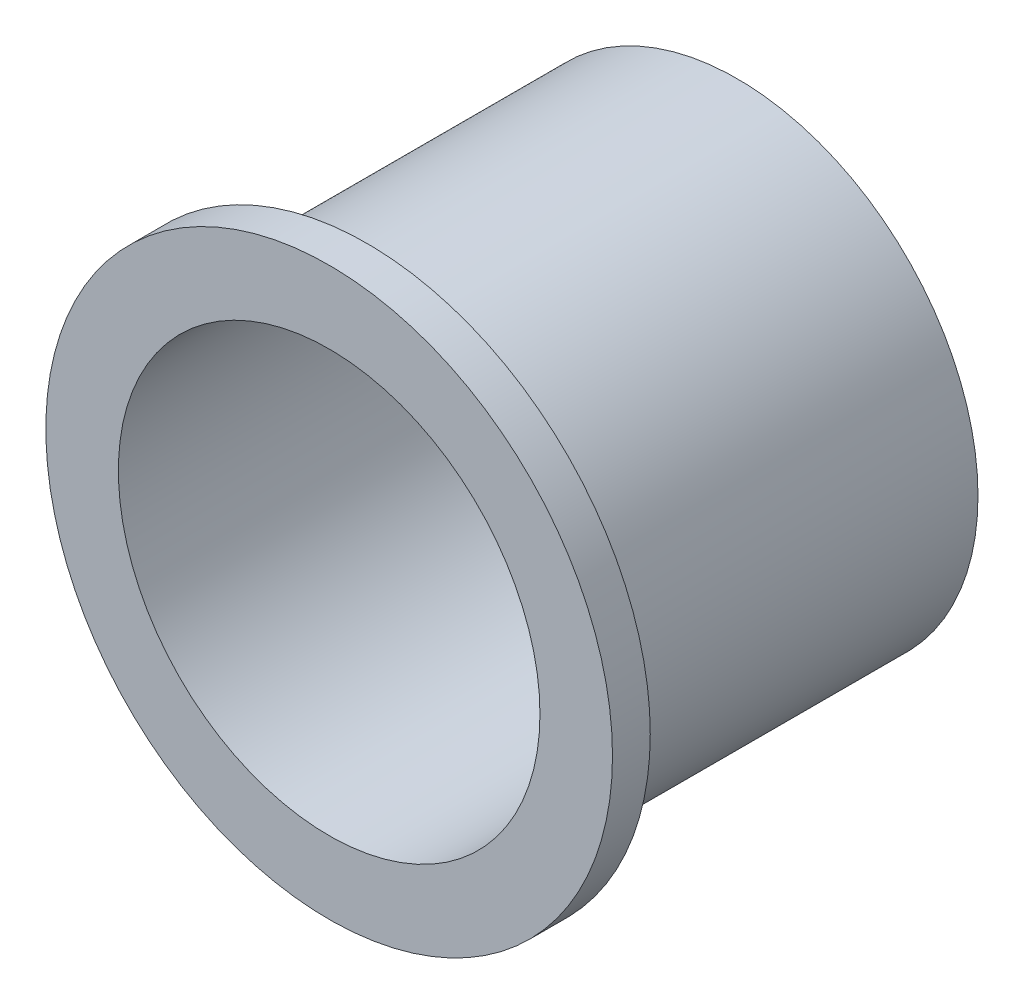
SolidWorks part; units mm, degrees
material "PE High Density"
ref_plane "Front Plane" through (0, 0, 0) normal (0, 0, 1) x (1, 0, 0)
ref_plane "Top Plane" through (0, 0, 0) normal (0, 1, 0) x (1, 0, 0)
ref_plane "Right Plane" through (0, 0, 0) normal (1, 0, 0) x (0, 0, -1)
sketch "Revolve Sketch" plane through (0, 0, 0) normal (1, 0, 0) x (0, 0, -1)
  line L0 (0, 190.5) -> (0, 141.732)
  line L1 (0, 141.732) -> (274.32, 141.732)
  line L2 (274.32, 141.732) -> (274.32, 161.925)
  line L3 (274.32, 161.925) -> (25.4, 161.925)
  line L4 (25.4, 161.925) -> (25.4, 190.5)
  line L5 (25.4, 190.5) -> (0, 190.5)
  line L6 (0, 0) -> (97.8064, 0) construction
  dimension "D1" = 141.732
  dimension "D2" = 161.925
  dimension "D3" = 190.5
  dimension "D4" = 25.4
  dimension "D5" = 274.32
revolve "Revolve Body" add sketch "Revolve Sketch" angle 360 about L6
equation "\"ID\"= 11.160in'for 12 NOM (EPG)"
equation "\"OD\"= 12.75'for 12 NOM (EPG)"
equation "\"A\"= 10.8in'refer to EPG datasheet"
equation "\"T\"= 1in'refer to EPG datasheet"
equation "\"C\"= 15in'refer to EPG datasheet"
equation "\"D1@Revolve Sketch\" = \"ID\" / 2"
equation "\"D2@Revolve Sketch\" = \"OD\" / 2"
equation "\"D3@Revolve Sketch\" = \"C\" / 2"
equation "\"D4@Revolve Sketch\" = \"T\""
equation "\"D5@Revolve Sketch\" = \"A\""
